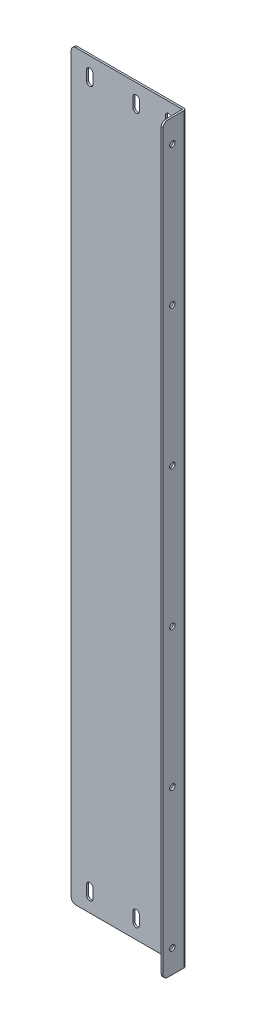
SolidWorks part; units mm, degrees
note: The reader was unsure of these and kept them because the rebuilt part matched: flange length of "边线-法兰1".
material "Q235-A"
ref_plane "前视基准面" through (0, 0, 0) normal (0, 0, 1) x (1, 0, 0)
ref_plane "上视基准面" through (0, 0, 0) normal (0, 1, 0) x (1, 0, 0)
ref_plane "右视基准面" through (0, 0, 0) normal (1, 0, 0) x (0, 0, -1)
sketch "草图1" plane through (0, 0, 0) normal (0, 0, 1) x (1, 0, 0)
  line L1 (122.5, -400) -> (-122.5, -400)
  line L2 (122.5, -400) -> (122.5, 400)
  line L3 (122.5, 400) -> (-122.5, 400)
  line L4 (-122.5, -400) -> (-122.5, 400)
  line L5 (122.5, -400) -> (-122.5, 400) construction
  line L6 (122.5, 400) -> (-122.5, -400) construction
  point P0 (0, 0)
  dimension "D1" = 245
  dimension "D2" = 800
base flange "基体-法兰1" sketch "草图1" thickness 2 reverse thickness direction no parameters "D1"=0.7366
fillet "圆角1" radius 5 4 edges at (122.5, 400, -1) (-122.5, 400, -1) (122.5, -400, -1) (-122.5, -400, -1)
sketch "草图2" plane through (0, 0, 0) normal (0, 0, 1) x (1, 0, 0)
  line L1 (0.5, -427.0069) -> (-0.5, -427.0069)
  line L2 (0.5, -427.0069) -> (0.5, 427.0069)
  line L3 (0.5, 427.0069) -> (-0.5, 427.0069)
  line L4 (-0.5, -427.0069) -> (-0.5, 427.0069)
  line L5 (0.5, -427.0069) -> (-0.5, 427.0069) construction
  line L6 (0.5, 427.0069) -> (-0.5, -427.0069) construction
  point P0 (0, 0)
  dimension "D1" = 1
extrude "切除-拉伸1" cut sketch "草图2" against normal blind 10 normal cut yes
sketch "草图3" plane through (0, 0, 0) normal (0, 0, 1) x (1, 0, 0)
  line L1 (0.5, 400) -> (130.5, 400)
  line L2 (0.5, 400) -> (0.5, -400.3202)
  line L3 (0.5, -400.3202) -> (130.5, -400.3202)
  line L4 (130.5, 400) -> (130.5, -400.3202)
  dimension "D1" = 130
extrude "切除-拉伸2" cut sketch "草图3" against normal blind 10
edge flange "边线-法兰1" sketch "草图8" flange angle 90 flange length 25 flange position material inside bend radius 0.7366 thickness 2 relief rectangular parameters "D6"=10
sketch "草图8" plane through (-0.5, 0, 0) normal (1, 0, 0) x (0, 1, 0)
  line L0 (400, 0) -> (-400, 0) construction
  line L1 (400, 0) -> (-400, 0)
  line L2 (-400, 0) -> (-400, 23)
  line L3 (-400, 23) -> (400, 23)
  line L4 (400, 23) -> (400, 0)
bend "边线折弯1" bend radius 0.7366 bend angle 90 parameters "D5"=1
fillet "圆角2" radius 5 2 edges at (-1.5, 400, 23) (-1.5, -400, 23)
sketch "草图9" plane through (0, 0, 0) normal (0, 0, 1) x (1, 0, 0)
  line L0 (-102.5, 385) -> (-102.5, 375) construction
  line L1 (-99, 385) -> (-99, 375)
  line L2 (-106, 385) -> (-106, 375)
  line L3 (-52.5, 385) -> (-52.5, 375) construction
  line L4 (-49, 385) -> (-49, 375)
  line L5 (-56, 385) -> (-56, 375)
  line L6 (-102.5, -385) -> (-102.5, -375) construction
  line L7 (-106, -385) -> (-106, -375)
  line L8 (-99, -385) -> (-99, -375)
  line L9 (-52.5, -385) -> (-52.5, -375) construction
  line L12 (-122.5, 395) -> (-122.5, -395) construction
  line L13 (-17.5, 375) -> (-17.5, 385) construction
  line L14 (-21, 375) -> (-21, 385)
  line L15 (-14, 375) -> (-14, 385)
  line L16 (-17.5, -375) -> (-17.5, -385) construction
  line L17 (-14, -375) -> (-14, -385)
  line L18 (-21, -375) -> (-21, -385)
  line L19 (-56, -385) -> (-56, -375)
  line L20 (-49, -385) -> (-49, -375)
  arc A0 (-99, 385) -> (-106, 385) centre (-102.5, 385) ccw
  arc A1 (-106, 375) -> (-99, 375) centre (-102.5, 375) ccw
  arc A2 (-49, 385) -> (-56, 385) centre (-52.5, 385) ccw
  arc A3 (-56, 375) -> (-49, 375) centre (-52.5, 375) ccw
  arc A4 (-106, -385) -> (-99, -385) centre (-102.5, -385) ccw
  arc A5 (-99, -375) -> (-106, -375) centre (-102.5, -375) ccw
  arc A8 (-21, 375) -> (-14, 375) centre (-17.5, 375) ccw
  arc A9 (-14, 385) -> (-21, 385) centre (-17.5, 385) ccw
  arc A10 (-14, -375) -> (-21, -375) centre (-17.5, -375) ccw
  arc A11 (-21, -385) -> (-14, -385) centre (-17.5, -385) ccw
  arc A12 (-56, -385) -> (-49, -385) centre (-52.5, -385) ccw
  arc A13 (-49, -375) -> (-56, -375) centre (-52.5, -375) ccw
  point P2 (-102.5, 380)
  point P8 (-52.5, 380)
  point P15 (-102.5, -380)
  point P22 (-52.5, -380)
  point P33 (-17.5, 380)
  point P39 (-17.5, -380)
  dimension "D12" = 50
  dimension "D17" = 35
  dimension "D18" = 760
  dimension "D5" = 35
  dimension "D1" = 7
  dimension "D2" = 7
  dimension "D3" = 10
  dimension "D4" = 10
  dimension "D6" = 10
  dimension "D7" = 7
  dimension "D8" = 7
  dimension "D9" = 10
  dimension "D10" = 380
  dimension "D11" = 20
  dimension "D13" = 7
  dimension "D14" = 10
  dimension "D15" = 7
  dimension "D16" = 10
extrude "切除-拉伸3" cut sketch "草图9" against normal blind 10 normal cut yes
hole_wizard "Ø6.0 (6) 直径孔1" positions "草图10" profile "草图11" hole size "Ø6.0" standard "GB" end condition through all
sketch "草图10" plane through (-2.5, 0, 0) normal (-1, 0, 0) x (0, 0, 1)
  line L0 (0.7366, 400) -> (18, 400) construction
  line L1 (23, 395) -> (23, -395) construction
  point P0 (13, 375)
  dimension "D1" = 25
  dimension "D2" = 10
sketch "草图11" plane through (-2.5, 375, 13) normal (0, 1, 0) x (0, 0, 1)
  line L0 (0, 0) -> (0, 2)
  line L1 (0, 2) -> (3, 2)
  line L2 (3, 2) -> (3, 0)
  line L5 (3, 0) -> (0, 0)
  line L11 (0, -6.35) -> (0, 107.95) construction
  dimension "通孔孔直径" = 6
  dimension "通孔孔深度" = 2
pattern_linear "阵列(线性)1" count 6 spacing 150 along (0, -1, 0) of "Ø6.0 (6) 直径孔1"
sketch "折弯-线1" [suppressed] plane through (0, 0, 0) normal (0, 1, 0) x (1, 0, 0)
sketch "边界框1" [suppressed] plane through (0, 0, 0) normal (0, 1, 0) x (1, 0, 0)
sheet metal parameters "钣金1" thickness 2 parameters "D1"=0.7366
flat pattern "平板型式1" [suppressed]
sketch "折弯-线2" plane through (0, 0, 0) normal (0, 1, 0) x (1, 0, 0)
sketch3d "边界框2" [suppressed]
  line L0 (122.5, -400, 0) -> (122.5, 400, 0) construction
  line L1 (-122.5, -400, 0) -> (-122.5, 400, 0) construction
  line L2 (122.5, -400, 0) -> (-122.5, -400, 0) construction
  line L3 (122.5, 400, 0) -> (-122.5, 400, 0) construction
sheet metal parameters "钣金3" thickness 2 parameters "D1"=0.7366
flat pattern "平板型式3"
sketch "折弯-线3" plane through (0, 0, 0) normal (0, 1, 0) x (1, 0, 0)
sketch3d "边界框3" [suppressed]
  line L0 (-0.5001, -400, 0) -> (-0.5, 400, 0) construction
  line L1 (-122.5, -400, 0) -> (-122.4999, 400, 0) construction
  line L2 (-0.5001, -400, 0) -> (-122.5, -400, 0) construction
  line L3 (-0.5, 400, 0) -> (-122.4999, 400, 0) construction
sheet metal parameters "钣金4" thickness 2 parameters "D1"=0.7366
flat pattern "平板型式4"
sketch "折弯-线4" plane through (0, 0, 0) normal (0, 1, 0) x (1, 0, 0)
sketch "边界框4" [suppressed] plane through (0, 0, 0) normal (0, 1, 0) x (1, 0, 0)
sheet metal parameters "钣金5" thickness 2 parameters "D1"=0.7366
flat pattern "平板型式3"
sketch "折弯-线3" plane through (0, 0, 0) normal (0, 0, 1) x (1, 0, 0)
  line L0 (-1.8727, -400) -> (-1.8727, 400) construction
  line L1 (-1.8727, -400) -> (-1.8727, 400) construction
sketch3d "边界框3" [suppressed]
  line L0 (21.7546, -400, 0) -> (21.7546, 400, 0) construction
  line L1 (-122.5, -400, 0) -> (-122.4999, 400, 0) construction
  line L2 (21.7546, -400, 0) -> (-122.5, -400, 0) construction
  line L3 (21.7546, 400, 0) -> (-122.4999, 400, 0) construction
bend of the flat pattern "展平-<边线折弯1>1"
sheet metal parameters "钣金6" thickness 2 parameters "D1"=0.7366
flat pattern "平板型式3"
sketch "折弯-线3" plane through (0, 0, 0) normal (0, 0, 1) x (1, 0, 0)
  line L0 (-1.8727, -400) -> (-1.8727, 400) construction
  line L1 (-1.8727, -400) -> (-1.8727, 400) construction
sketch3d "边界框3" [suppressed]
  line L0 (21.7546, -400, 0) -> (21.7546, 400, 0) construction
  line L1 (-122.5, -400, 0) -> (-122.4999, 400, 0) construction
  line L2 (21.7546, -400, 0) -> (-122.5, -400, 0) construction
  line L3 (21.7546, 400, 0) -> (-122.4999, 400, 0) construction
bend of the flat pattern "展平-<边线折弯1>1"
sheet metal parameters "钣金7" thickness 2 parameters "D1"=0.7366
flat pattern "平板型式3"
sketch "折弯-线3" plane through (0, 0, 0) normal (0, 0, 1) x (1, 0, 0)
  line L0 (-1.8727, -400) -> (-1.8727, 400) construction
  line L1 (-1.8727, -400) -> (-1.8727, 400) construction
sketch3d "边界框3" [suppressed]
  line L0 (21.7546, -400, 0) -> (21.7546, 400, 0) construction
  line L1 (-122.5, -400, 0) -> (-122.4999, 400, 0) construction
  line L2 (21.7546, -400, 0) -> (-122.5, -400, 0) construction
  line L3 (21.7546, 400, 0) -> (-122.4999, 400, 0) construction
bend of the flat pattern "展平-<边线折弯1>1"
sheet metal parameters "钣金8" thickness 2 parameters "D1"=0.7366
flat pattern "平板型式3"
sketch "折弯-线3" plane through (0, 0, 0) normal (0, 0, 1) x (1, 0, 0)
  line L0 (-1.8727, -400) -> (-1.8727, 400) construction
  line L1 (-1.8727, -400) -> (-1.8727, 400) construction
sketch3d "边界框3" [suppressed]
  line L0 (21.7546, -400, 0) -> (21.7546, 400, 0) construction
  line L1 (-122.5, -400, 0) -> (-122.4999, 400, 0) construction
  line L2 (21.7546, -400, 0) -> (-122.5, -400, 0) construction
  line L3 (21.7546, 400, 0) -> (-122.4999, 400, 0) construction
bend of the flat pattern "展平-<边线折弯1>1"
